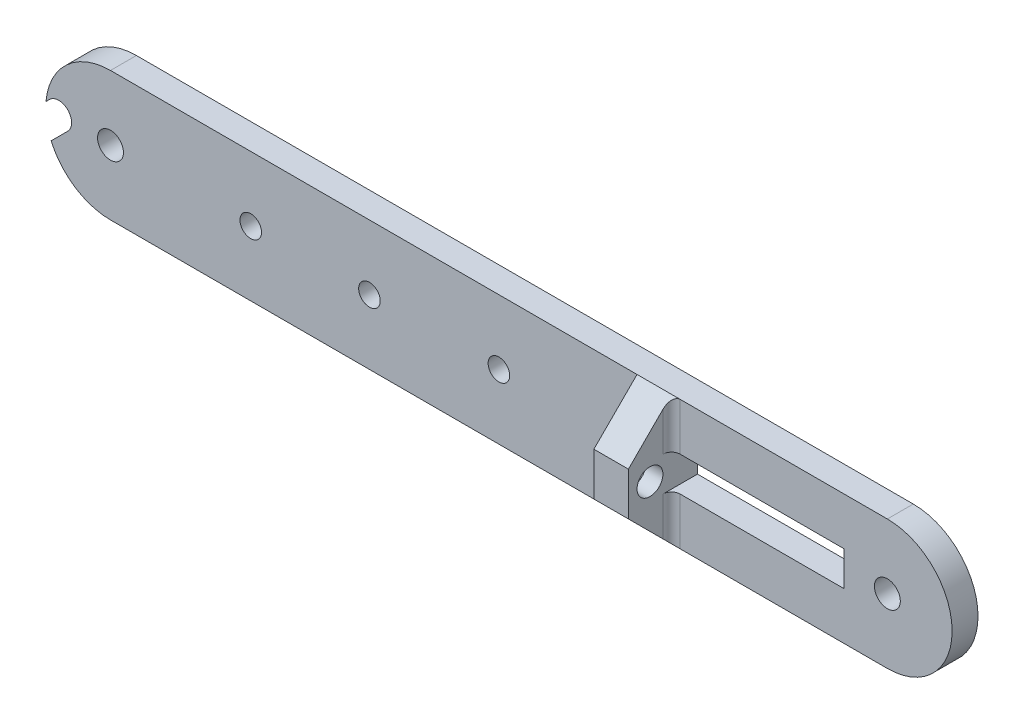
SolidWorks part; units mm, degrees
ref_plane "Plan de face" through (0, 0, 0) normal (0, 0, 1) x (1, 0, 0)
ref_plane "Plan de dessus" through (0, 0, 0) normal (0, 1, 0) x (1, 0, 0)
ref_plane "Plan de droite" through (0, 0, 0) normal (1, 0, 0) x (0, 0, -1)
sketch "Esquisse1" plane through (0, 0, 0) normal (0, 0, 1) x (1, 0, 0)
  line L0 (-74.3787, 0) -> (69.7437, 0) construction
  line L1 (0, 0) -> (0, 19.0596) construction
  line L2 (90, -15) -> (-90, -15)
  line L3 (90, 15) -> (-90, 15)
  line L5 (40, -4) -> (80, -4)
  line L6 (40, -4) -> (40, 4)
  line L7 (40, 4) -> (80, 4)
  line L8 (80, -4) -> (80, 4)
  line L9 (40, -4) -> (80, 4) construction
  line L10 (40, 4) -> (80, -4) construction
  arc A0 (90, -15) -> (90, 15) centre (90, 0) ccw
  circle A1 centre (90, 0) radius 3
  circle A2 centre (-90, 0) radius 3
  arc A3 (-90, -15) -> (-90, 15) centre (-90, 0) cw
  circle A4 centre (0, 0) radius 2.5
  circle A5 centre (-57.5, 0) radius 2.5
  circle A6 centre (-30, 0) radius 2.5
  point P4 (60, 0)
  point P17 (0, -15)
  point P20 (0, 15)
  dimension "D1" = 30
  dimension "D3" = 6
  dimension "D7" = 5
  dimension "D8" = 5
  dimension "D9" = 5
  dimension "D2" = 90
  dimension "D4" = 8
  dimension "D5" = 40
  dimension "D6" = 60
  dimension "D10" = 30
  dimension "D11" = 30
extrude "Boss.-Extru.1" add sketch "Esquisse1" along normal blind 6
sketch "Esquisse2" plane through (40, 0, 0) normal (1, 0, 0) x (0, 0, -1)
  line L0 (0, -4) -> (-6, 4) construction
  line L1 (-6, 4) -> (-6, 0) construction
  line L2 (-6, 4) -> (-6, -4) construction
  line L3 (-6, 0) -> (-15.5036, 0) construction
  line L4 (-6, 15) -> (-6, -15) construction
  line L6 (-16, 5) -> (-16, -5)
  line L8 (-6, 5) -> (-6, -5)
  line L9 (-16, 5) -> (-6, -5) construction
  line L10 (-16, -5) -> (-6, 5) construction
  line L11 (-6, -15) -> (-16, -5)
  line L12 (-6, -15) -> (-6, -5)
  line L13 (-6, 5) -> (-6, 15)
  line L14 (-6, 15) -> (-16, 5)
  circle A0 centre (-11, 0) radius 3
  point P7 (-11, 0)
  dimension "D3" = 6
  dimension "D1" = 10
  dimension "D2" = 10
extrude "Boss.-Extru.2" add sketch "Esquisse2" against normal blind 8
fillet "Congé2" radius 2 2 edges
sketch "Esquisse3" plane through (32, 0, 0) normal (-1, 0, 0) x (0, 0, 1)
  line L0 (11, 0) -> (11, 4) construction
  line L1 (11, 0) -> (14.4641, 2) construction
  line L2 (11, 0) -> (14.4641, -2) construction
  line L3 (11, 4) -> (14.4641, 2)
  line L4 (14.4641, 2) -> (14.4641, -2)
  line L5 (14.4641, -2) -> (11, -4)
  line L6 (7.5359, 2) -> (7.5359, -2)
  line L7 (11, 4) -> (7.5359, 2)
  line L8 (7.5359, -2) -> (11, -4)
  dimension "D2" = 60
  dimension "D3" = 60
extrude "Enlèv. mat.-Extru.1" cut sketch "Esquisse3" against normal blind 4
sketch "Esquisse4" plane through (0, 0, 6) normal (0, 0, 1) x (1, 0, 0)
  line L0 (-90, 0) -> (-105, 0) construction
  line L1 (-105, 0) -> (-102, 0) construction
  line L2 (-102, 0) -> (-99.8787, -2.1213) construction
  line L3 (-99.8787, -2.1213) -> (-104.1213, 2.1213)
  line L4 (-99.8787, -2.1213) -> (-104.1213, 2.1213)
  line L5 (-99.8787, -2.1213) -> (-104.2614, -6.504)
  line L6 (-104.1213, 2.1213) -> (-108.504, -2.2614)
  line L7 (-104.2614, -6.504) -> (-108.504, -2.2614)
  arc A0 (-90, 15) -> (-90, -15) centre (-90, 0) ccw construction
  circle A1 centre (-102, 0) radius 3
  arc M9 (-90, 15) -> (-90, -15) centre (-90, 0) ccw
  dimension "D1" = 3
  dimension "D2" = 135
extrude "Enlèv. mat.-Extru.4" cut sketch "Esquisse4" against normal blind 10 contours L3 A1 | A1 L6 M9 | A1 L5 M9 | L3 A1 region at (-102.9003, -0.9003, 6) region at (-101.0997, 0.9003, 6) region at (-103.2777, -3.6386, 6) region at (-104.7977, 1.1965, 6)
